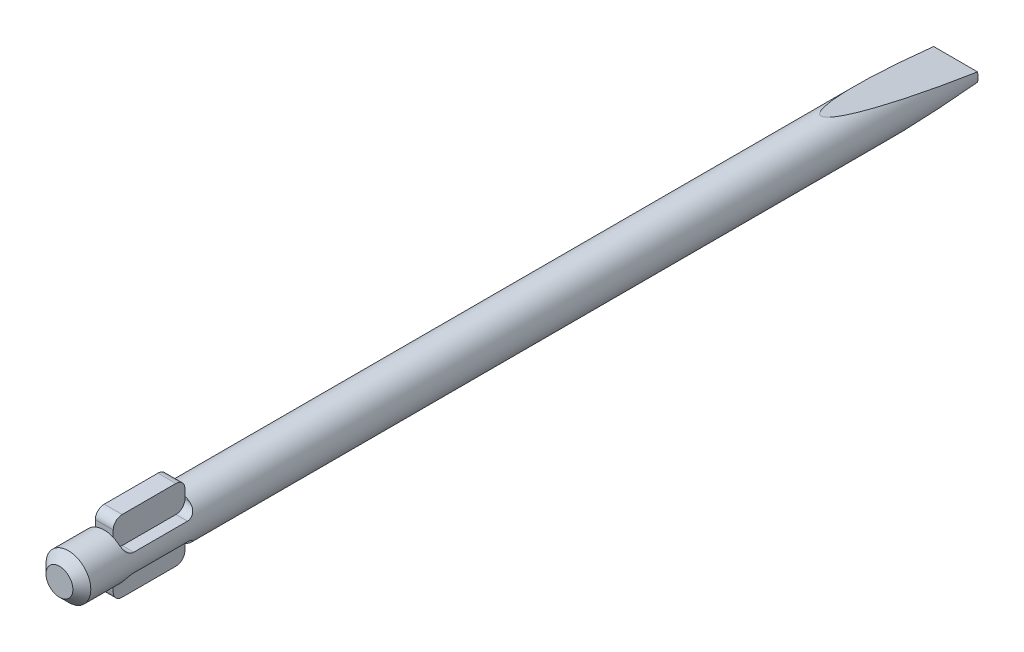
SolidWorks part; units mm, degrees
ref_plane "Front Plane" through (0, 0, 0) normal (0, 0, 1) x (1, 0, 0)
ref_plane "Top Plane" through (0, 0, 0) normal (0, 1, 0) x (1, 0, 0)
ref_plane "Right Plane" through (0, 0, 0) normal (1, 0, 0) x (0, 0, -1)
sketch "Sketch1" plane through (0, 0, 0) normal (0, 0, 1) x (1, 0, 0)
  circle A0 centre (0, 0) radius 2.5
  dimension "D1" = 5
extrude "Boss-Extrude1" add sketch "Sketch1" along normal blind 100
sketch "Sketch2" plane through (0, 0, 0) normal (1, 0, 0) x (0, 0, -1)
  line L0 (-100, 2.5) -> (-100, -2.5) construction
  line L1 (-94, 4) -> (-88, 4)
  line L2 (-95, 3) -> (-95, 2)
  line L3 (-94, 1) -> (-88, 1)
  line L4 (-87, 3) -> (-87, 2)
  line L5 (-100, 0) -> (-77.6887, 0) construction
  line L6 (-87, -3) -> (-87, -2)
  line L7 (-94, -1) -> (-88, -1)
  line L8 (-95, -3) -> (-95, -2)
  line L9 (-94, -4) -> (-88, -4)
  arc A0 (-95, 2) -> (-94, 1) centre (-94, 2) ccw
  arc A1 (-94, 4) -> (-95, 3) centre (-94, 3) ccw
  arc A2 (-88, 4) -> (-87, 3) centre (-88, 3) cw
  arc A3 (-88, 1) -> (-87, 2) centre (-88, 2) ccw
  arc A4 (-88, -1) -> (-87, -2) centre (-88, -2) cw
  arc A5 (-95, -2) -> (-94, -1) centre (-94, -2) cw
  arc A6 (-88, -4) -> (-87, -3) centre (-88, -3) ccw
  arc A7 (-94, -4) -> (-95, -3) centre (-94, -3) cw
  point P13 (-95, 4)
  point P16 (-87, 4)
  point P19 (-87, 1)
  point P32 (-95, -4)
  dimension "D5" = 1
  dimension "D1" = 3
  dimension "D2" = 8
  dimension "D3" = 5
  dimension "D4" = 1
extrude "Cut-Extrude1" cut sketch "Sketch2" against normal mid plane 10
extrude "Boss-Extrude2" add sketch "Sketch2<2>" along normal mid plane 2
sketch "Sketch2<2>" plane through (0, 0, 0) normal (1, 0, 0) x (0, 0, -1) same geometry as "Sketch2"
chamfer "Chamfer1" distance 1 angle 45 1 edges at (2.5, 0, 100)
sketch "Sketch3" plane through (0, 0, 0) normal (1, 0, 0) x (0, 0, -1)
  line L0 (0, 0.5) -> (0, -0.5)
  line L1 (0, -2.5) -> (0, 2.5) construction
  line L2 (0, -0.5) -> (-15, -2.5)
  line L3 (0, 0.5) -> (-15, 2.5)
  line L5 (0, 2.5) -> (-87, 2.5) construction
  line L6 (-15, 2.5) -> (0, 2.5)
  line L7 (0, 2.5) -> (0, -2.5)
  line L8 (0, -2.5) -> (-15, -2.5)
  line L9 (-87, -2.5) -> (0, -2.5) construction
  line L10 (-87, -2.5) -> (0, -2.5)
  point P6 (0, 0)
  point P12 (0, 0.5)
  point P19 (0, 0)
  dimension "D1" = 1
  dimension "D2" = 15
  dimension "D3" = 15
extrude "Cut-Extrude2" cut sketch "Sketch3" against normal through all and the other way through all contours L7 L6 L3 | L8 L7 L2 region at (0, -1.8333, 5) region at (0, 1.8333, 5)
